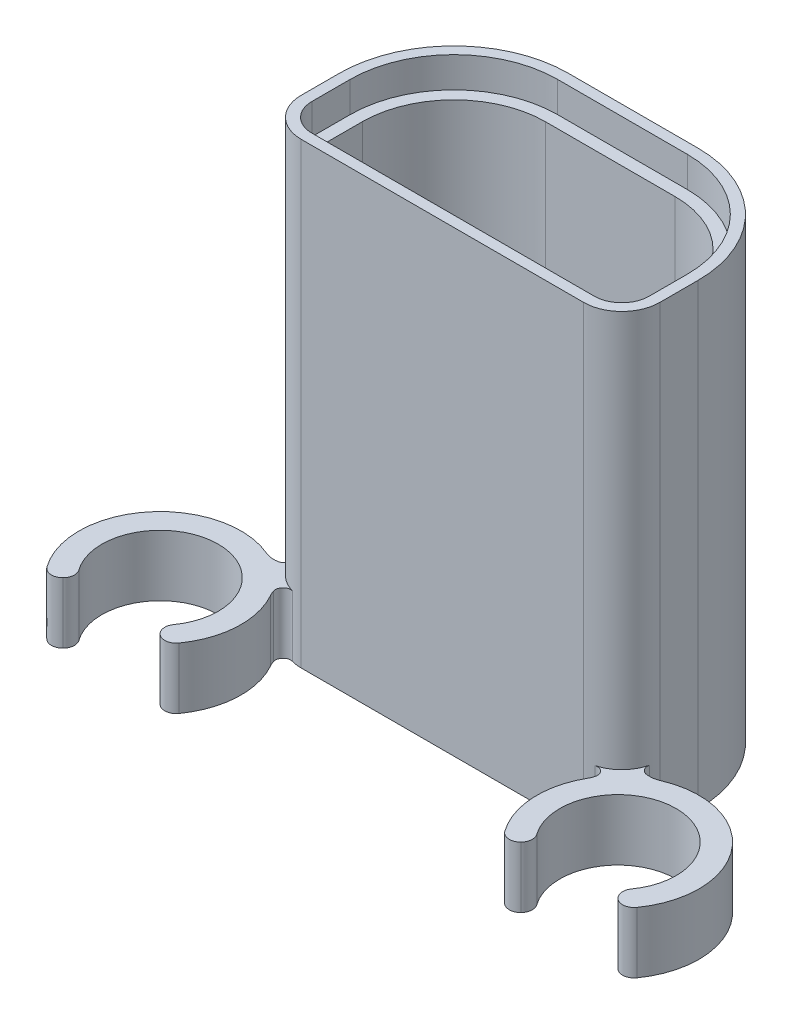
SolidWorks part; units mm, degrees
ref_plane "Front Plane" through (0, 0, 0) normal (0, 0, 1) x (1, 0, 0)
ref_plane "Top Plane" through (0, 0, 0) normal (0, 1, 0) x (1, 0, 0)
ref_plane "Right Plane" through (0, 0, 0) normal (1, 0, 0) x (0, 0, -1)
sketch "Sketch1" plane through (0, 0, 0) normal (0, 1, 0) x (1, 0, 0)
  line L0 (-23.5, 12.5) -> (23.5, 12.5)
  line L1 (-20.5, -9.5) -> (20.5, -9.5) construction
  line L2 (-20.5, -9.5) -> (-20.5, 9.5) construction
  line L3 (-20.5, 9.5) -> (20.5, 9.5) construction
  line L4 (20.5, -9.5) -> (20.5, 9.5) construction
  line L5 (-20.5, -9.5) -> (20.5, 9.5) construction
  line L6 (-20.5, 9.5) -> (20.5, -9.5) construction
  line L7 (23.5, -12.5) -> (23.5, 12.5)
  line L8 (-23.5, -12.5) -> (23.5, -12.5)
  line L9 (-23.5, -12.5) -> (-23.5, 12.5)
  point P0 (0, 0)
  dimension "D1" = 19
  dimension "D2" = 41
  dimension "D3" = 3
extrude "Boss-Extrude1" add sketch "Sketch1" along normal blind 60
shell "Shell1" thickness 3 removed face at (0, 60, 0)
sketch "Sketch2" plane through (0, 0, 0) normal (0, 1, 0) x (1, 0, 0)
  line L0 (0, 0) -> (-30, 0) construction
  line L1 (0, 0) -> (0, 6.7838) construction
  circle A0 centre (-30, 0) radius 7.625
  circle A1 centre (30, 0) radius 7.625
  dimension "D1" = 15.25
  dimension "D2" = 30
extrude "Cut-Extrude3" [suppressed] cut sketch "Sketch2" along normal through all
sketch "Sketch3" [suppressed] plane through (0, 0, 0) normal (0, 1, 0) x (1, 0, 0)
  line L0 (-20.5, 4.7582) -> (-20.5, -4.7582)
  line L1 (-26.5, 10.032) -> (-26.5, 6.7743)
  line L2 (-26.5, -6.7743) -> (-26.5, -10.032)
  line L3 (-23.5, 12.5) -> (-23.5, 3.9863) construction
  line L4 (0, 0) -> (0, 12.5) construction
  line L5 (23.5, 12.5) -> (-23.5, 12.5) construction
  line L6 (26.5, -6.7743) -> (26.5, -10.032)
  line L7 (26.5, 10.032) -> (26.5, 6.7743)
  line L8 (20.5, 4.7582) -> (20.5, -4.7582)
  arc A0 (-26.5, -6.7743) -> (-26.5, 6.7743) centre (-30, 0) ccw
  arc A1 (-20.5, 4.7582) -> (-26.5, 10.032) centre (-30, 0) ccw
  arc A2 (-26.5, -10.032) -> (-20.5, -4.7582) centre (-30, 0) ccw
  arc A3 (26.5, -10.032) -> (20.5, -4.7582) centre (30, 0) cw
  arc A4 (20.5, 4.7582) -> (26.5, 10.032) centre (30, 0) cw
  arc A5 (26.5, -6.7743) -> (26.5, 6.7743) centre (30, 0) cw
  dimension "D1" = 3
  dimension "D4" = 7.625
  dimension "D2" = 3
  dimension "D3" = 30
extrude "Boss-Extrude2" [suppressed] add sketch "Sketch3" along normal blind 67
fillet "Fillet1" [suppressed] radius 1
sketch "Sketch4" plane through (0, 0, 0) normal (0, -1, 0) x (1, 0, 0)
  line L0 (0, 12.5) -> (0, 2) construction
  line L1 (-23.5, 12.5) -> (23.5, 12.5) construction
  line L2 (6, 6.75) -> (6, 2.25)
  line L3 (-15.5, 6.75) -> (-6, 6.75)
  line L4 (-15.5, 6.75) -> (-15.5, 2.25)
  line L5 (-15.5, 2.25) -> (-6, 2.25)
  line L6 (-6, 6.75) -> (-6, 2.25)
  line L7 (15.5, 2.25) -> (6, 2.25)
  line L8 (15.5, 6.75) -> (15.5, 2.25)
  line L9 (15.5, 6.75) -> (6, 6.75)
  circle A0 centre (0, 2) radius 3
  dimension "D2" = 6
  dimension "D1" = 10.5
  dimension "D3" = 15.5
  dimension "D4" = 5.75
  dimension "D5" = 4.5
extrude "Cut-Extrude4" [suppressed] cut sketch "Sketch4" against normal through all
fillet "Fillet2" radius 12 2 edges at (20.5, 31.5, -9.5) (-20.5, 31.5, -9.5)
fillet "Fillet3" radius 15 2 edges at (23.5, 30, -12.5) (-23.5, 30, -12.5)
sketch "Sketch5" plane through (0, 0, 0) normal (0, 1, 0) x (1, 0, 0)
  line L0 (0, -12.5) -> (0, -19.5) construction
  line L1 (-23.5, -12.5) -> (23.5, -12.5) construction
  line L2 (0, -19.5) -> (-30, -19.5) construction
  line L3 (-30, -19.5) -> (0, 12.5) construction
  line L4 (8.5, 12.5) -> (-8.5, 12.5) construction
  line L5 (-24.1091, -10.6576) -> (-23.0238, -9.5)
  line L6 (-18.8171, -9.5) -> (-23.0238, -9.5)
  line L7 (-21.8511, -12.682) -> (-18.8171, -9.5)
  line L8 (21.8511, -12.682) -> (18.8171, -9.5)
  line L9 (18.8171, -9.5) -> (23.0238, -9.5)
  line L10 (24.1091, -10.6576) -> (23.0238, -9.5)
  line L11 (-20.5, -9.5) -> (20.5, -9.5) construction
  circle A0 centre (-30, -19.5) radius 7.625
  arc A1 (-24.1091, -10.6576) -> (-21.8511, -12.682) centre (-30, -19.5) ccw
  arc A2 (24.1091, -10.6576) -> (21.8511, -12.682) centre (30, -19.5) cw
  circle A3 centre (30, -19.5) radius 7.625
  dimension "D3" = 15.25
  dimension "D4" = 21.25
  dimension "D1" = 7
  dimension "D2" = 30
  dimension "D5" = 1.75
  dimension "D6" = 0
extrude "Boss-Extrude3" add sketch "Sketch5" along normal blind 8
fillet "Fillet7" radius 2 2 edges at (-20.5, 31.5, 9.5) (20.5, 31.5, 9.5)
fillet "Fillet8" radius 5 2 edges at (-23.5, 34, 12.5) (23.5, 34, 12.5)
fillet "Fillet9" radius 3 2 edges at (-24.1091, 4, 10.6576) (24.1091, 4, 10.6576)
fillet "Fillet10" radius 3 2 edges at (-21.8511, 4, 12.682) (21.8511, 4, 12.682)
fillet "Fillet11" radius 1 4 edges at (23.0637, 4, 9.5426) (21.025, 4, 11.8156) (-23.0637, 4, 9.5426) (-21.025, 4, 11.8156)
sketch "Sketch6" plane through (0, 60, 0) normal (0, 1, 0) x (1, 0, 0)
  line L26 (22.1, -7.5) -> (22.1, -2.5)
  line L27 (-18.5, -11.1) -> (18.5, -11.1)
  line L28 (-22.1, -2.5) -> (-22.1, -7.5)
  line L29 (8.5, 11.1) -> (-8.5, 11.1)
  line L30 (22.1, -7.5) -> (22.1, -2.5)
  line L31 (-18.5, -11.1) -> (18.5, -11.1)
  line L32 (-22.1, -2.5) -> (-22.1, -7.5)
  line L33 (8.5, 11.1) -> (-8.5, 11.1)
  arc A21 (22.1, -2.5) -> (8.5, 11.1) centre (8.5, -2.5) ccw
  arc A22 (18.5, -11.1) -> (22.1, -7.5) centre (18.5, -7.5) ccw
  arc A23 (-22.1, -7.5) -> (-18.5, -11.1) centre (-18.5, -7.5) ccw
  arc A24 (-8.5, 11.1) -> (-22.1, -2.5) centre (-8.5, -2.5) ccw
  arc A25 (22.1, -2.5) -> (8.5, 11.1) centre (8.5, -2.5) ccw
  arc A26 (18.5, -11.1) -> (22.1, -7.5) centre (18.5, -7.5) ccw
  arc A27 (-22.1, -7.5) -> (-18.5, -11.1) centre (-18.5, -7.5) ccw
  arc A28 (-8.5, 11.1) -> (-22.1, -2.5) centre (-8.5, -2.5) ccw
  dimension "D1" = 1.6
extrude "Cut-Extrude5" cut sketch "Sketch6" against normal blind 4
sketch "Sketch7" plane through (0, 3, 0) normal (0, 1, 0) x (1, 0, 0)
  line L0 (-20.5, -2.5) -> (-20.5, -7.5) construction
  line L1 (-20.5, -8) -> (20.5, -8)
  line L2 (-20.5, -8) -> (-20.5, -3)
  line L3 (-20.5, -3) -> (-15.5, -3)
  line L4 (20.5, -8) -> (20.5, -3)
  line L5 (20.5, -7.5) -> (20.5, -2.5) construction
  line L6 (-18.5, -9.5) -> (18.5, -9.5) construction
  line L7 (15.5, -3) -> (20.5, -3)
  line L9 (-13.5, -1) -> (-13.5, 5)
  line L10 (-11.5, 7) -> (11.5, 7)
  line L11 (13.5, -1) -> (13.5, 5)
  arc A0 (15.5, -3) -> (13.5, -1) centre (15.5, -1) cw
  arc A1 (11.5, 7) -> (13.5, 5) centre (11.5, 5) cw
  arc A2 (-13.5, 5) -> (-11.5, 7) centre (-11.5, 5) cw
  arc A3 (-15.5, -3) -> (-13.5, -1) centre (-15.5, -1) ccw
  dimension "D6" = 2
  dimension "D1" = 1.5
  dimension "D2" = 5
  dimension "D3" = 7
  dimension "D4" = 7
  dimension "D5" = 10
extrude "Cut-Extrude6" cut sketch "Sketch7" against normal blind 1 and the other way blind 70
sketch "Sketch8" plane through (0, 0, -12.5) normal (0, 0, -1) x (-1, 0, 0)
  line L0 (0, 0) -> (0, 68) construction
  line L1 (-8.5, 60) -> (8.5, 60) construction
  line L2 (0, 34) -> (-23.5, 34) construction
  line L3 (-23.5, 0) -> (-23.5, 60) construction
  line L5 (-7, 24) -> (7, 24)
  line L6 (-10, 27) -> (-10, 41)
  line L7 (-7, 44) -> (7, 44)
  line L8 (10, 27) -> (10, 41)
  line L9 (-10, 24) -> (10, 44) construction
  line L10 (-10, 44) -> (10, 24) construction
  circle A0 centre (0, 34) radius 6.5
  circle A1 centre (0, 34) radius 5.5
  arc A2 (-7, 24) -> (-10, 27) centre (-7, 27) cw
  arc A3 (7, 24) -> (10, 27) centre (7, 27) ccw
  arc A4 (7, 44) -> (10, 41) centre (7, 41) cw
  arc A5 (-10, 41) -> (-7, 44) centre (-7, 41) cw
  dimension "D2" = 3
  dimension "D4" = 13
  dimension "D5" = 11
  dimension "D1" = 8
  dimension "D3" = 20
extrude "Cut-Extrude7" cut sketch "Sketch8" against normal blind 0.5 contours L7 A4 L8 A3 L5 A2 L6 A5 | A1
sketch "Sketch10" plane through (0, 0, -12) normal (0, 0, -1) x (-1, 0, 0)
  line L0 (0, 34) -> (0, 43.0017) construction
  line L1 (0.571, 42.1304) -> (-0.571, 42.1304)
  line L2 (-0.571, 42.1304) -> (-0.863, 40.6442)
  line L3 (0.571, 42.1304) -> (0.863, 40.6442)
  arc A0 (0.863, 40.6442) -> (-0.863, 40.6442) centre (0, 34) ccw
  point P9 (0, 42.1304)
extrude "Boss-Extrude4" add sketch "Sketch10" along normal blind 0.5
pattern_circular "CirPattern1" count 18 over 360 about axis through (0, 34, -12) along (0, 0, -1) of "Boss-Extrude4"
sketch "Sketch11" plane through (0, 0, -12) normal (0, 0, -1) x (-1, 0, 0)
  circle A0 centre (0, 34) radius 7.0864
  circle A1 centre (0, 34) radius 6.5559
extrude "Boss-Extrude5" add sketch "Sketch11" along normal blind 0.5
fillet "Fillet12" radius 0.5 82 edges at (-5.5, 34, -12) (-6.5559, 34, -12) (6.9091, 30.7937, -12) (7.0412, 29.9348, -12) (6.2313, 29.6196, -12) (5.4285, 29.445, -12) (5.3959, 28.624, -12) (5.2262, 27.7717, -12) (4.3573, 27.7526, -12) (3.5432, 27.863, -12) (3.2318, 27.1028, -12) (2.7808, 26.3599, -12) (1.9578, 26.6391, -12) (1.2305, 27.0213, -12) (0.6779, 26.4134, -12) (0, 25.8696, -12) (-0.6779, 26.4134, -12) (-1.2305, 27.0213, -12) (-1.9578, 26.6391, -12) (-2.7808, 26.3599, -12) (-3.2318, 27.1028, -12) (-3.5432, 27.863, -12) (-4.3573, 27.7526, -12) (-5.2262, 27.7717, -12) (-5.3959, 28.624, -12) (-5.4285, 29.445, -12) (-6.2313, 29.6196, -12) (-7.0412, 29.9348, -12) (-6.9091, 30.7937, -12) (-6.659, 31.5763, -12) (-7.3537, 32.015, -12) (-8.0069, 32.5882, -12) (-7.5891, 33.3502, -12) (-7.0864, 34, -12) (-7.5891, 34.6498, -12) (-8.0069, 35.4118, -12) (-7.3537, 35.985, -12) (-6.659, 36.4237, -12) (-6.9091, 37.2063, -12) (-7.0412, 38.0652, -12) (-6.2313, 38.3804, -12) (-5.4285, 38.555, -12) (-5.3959, 39.376, -12) (-5.2262, 40.2283, -12) (-4.3573, 40.2474, -12) (-3.5432, 40.137, -12) (-3.2318, 40.8972, -12) (-2.7808, 41.6401, -12) (-1.9578, 41.3609, -12) (-1.2305, 40.9787, -12) (-0.6779, 41.5866, -12) (0, 42.1304, -12) (0.6779, 41.5866, -12) (1.2305, 40.9787, -12) (1.9578, 41.3609, -12) (2.7808, 41.6401, -12) (3.2318, 40.8972, -12) (3.5432, 40.137, -12) (4.3573, 40.2474, -12) (5.2262, 40.2283, -12) (5.3959, 39.376, -12) (5.4285, 38.555, -12) (6.2313, 38.3804, -12) (7.0412, 38.0652, -12) (6.9091, 37.2063, -12) (6.659, 36.4237, -12) (7.3537, 35.985, -12) (8.0069, 35.4118, -12) (7.5891, 34.6498, -12) (7.0864, 34, -12) (7.5891, 33.3502, -12) (8.0069, 32.5882, -12) (7.3537, 32.015, -12) (6.659, 31.5763, -12) (0, 44, -12) (-9.1213, 43.1213, -12) (-10, 34, -12) (-9.1213, 24.8787, -12) (0, 24, -12) (9.1213, 24.8787, -12) (10, 34, -12) (9.1213, 43.1213, -12)
sketch "Sketch12" plane through (0, 0, 0) normal (0, -1, 0) x (1, 0, 0)
  line L0 (-30, 19.5) -> (-30, 34.8908) construction
  line L1 (-30, 19.5) -> (-43.9378, 33.4378)
  line L2 (-30, 19.5) -> (-16.0622, 33.4378)
  line L3 (-43.9378, 33.4378) -> (-16.0622, 33.4378)
  line L4 (0, 0) -> (0, 22.093) construction
  line L5 (30, 19.5) -> (30, 34.8908) construction
  line L6 (43.9378, 33.4378) -> (16.0622, 33.4378)
  line L7 (30, 19.5) -> (16.0622, 33.4378)
  line L8 (30, 19.5) -> (43.9378, 33.4378)
  dimension "D1" = 45
extrude "Cut-Extrude8" cut sketch "Sketch12" against normal blind 10
fillet "Fillet13" radius 1.5 8 edges at (37.513, 4, 27.013) (35.3917, 4, 24.8917) (24.6083, 4, 24.8917) (22.487, 4, 27.013) (-22.487, 4, 27.013) (-24.6083, 4, 24.8917) (-35.3917, 4, 24.8917) (-37.513, 4, 27.013)
